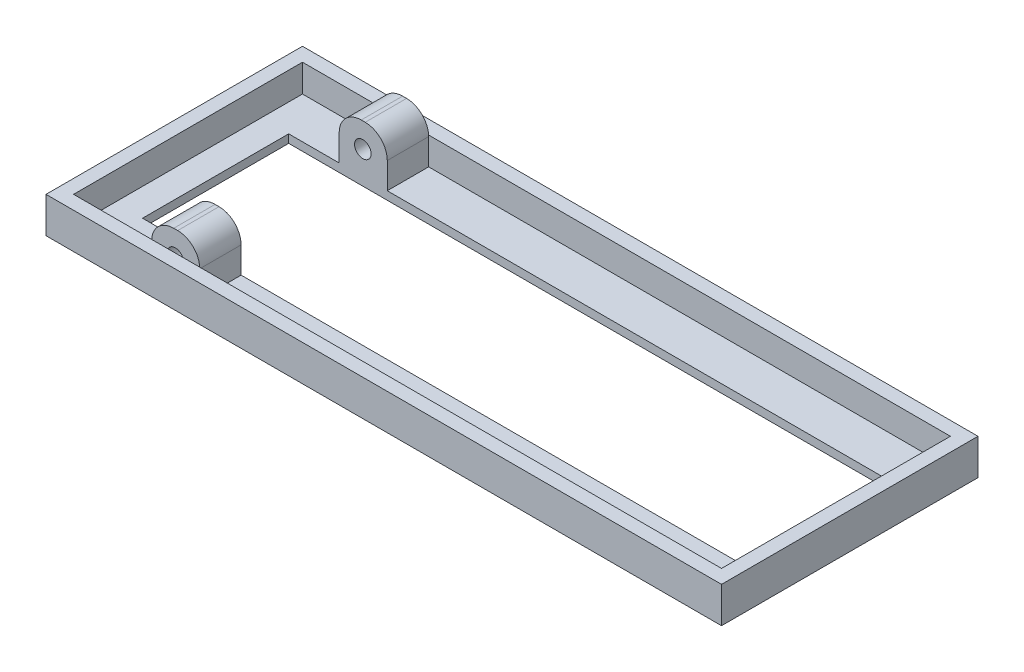
SolidWorks part; units mm, degrees
ref_plane "Front Plane" through (0, 0, 0) normal (0, 0, 1) x (1, 0, 0)
ref_plane "Top Plane" through (0, 0, 0) normal (0, 1, 0) x (1, 0, 0)
ref_plane "Right Plane" through (0, 0, 0) normal (1, 0, 0) x (0, 0, -1)
sketch "Sketch1" plane through (0, 0, 0) normal (0, 1, 0) x (1, 0, 0)
  line L0 (1125.8144, 1330.2208) -> (1275.8144, 1330.2208) construction
  line L1 (1275.8144, 1330.2208) -> (1275.8144, 1130.2208) construction
  line L2 (3575.3144, 400.2208) -> (3575.3144, 600.2208) construction
  line L3 (3575.3144, 600.2208) -> (3425.3144, 600.2208) construction
  line L5 (1275.8144, 1130.2208) -> (3425.3144, 1130.2208)
  line L6 (1275.8144, 1130.2208) -> (1275.8144, 600.2208)
  line L7 (1275.8144, 600.2208) -> (3425.3144, 600.2208)
  line L8 (3425.3144, 1130.2208) -> (3425.3144, 600.2208)
  line L13 (1125.8144, 1330.2208) -> (3575.3144, 1330.2208)
  line L14 (1125.8144, 1330.2208) -> (1125.8144, 400.2208)
  line L15 (1125.8144, 400.2208) -> (3575.3144, 400.2208)
  line L16 (3575.3144, 1330.2208) -> (3575.3144, 400.2208)
sketch "Sketch4" plane through (0, 0, 0) normal (0, 1, 0) x (1, 0, 0)
  line L0 (1125.8144, 1330.2208) -> (1275.8144, 1330.2208) construction
  line L1 (1275.8144, 1330.2208) -> (1275.8144, 1130.2208) construction
  line L2 (3575.3144, 400.2208) -> (3575.3144, 600.2208) construction
  line L3 (3575.3144, 600.2208) -> (3425.3144, 600.2208) construction
  line L4 (1275.8144, 1130.2208) -> (3425.3144, 1130.2208)
  line L5 (1275.8144, 1130.2208) -> (1275.8144, 600.2208)
  line L6 (1275.8144, 600.2208) -> (3425.3144, 600.2208)
  line L7 (3425.3144, 1130.2208) -> (3425.3144, 600.2208)
  line L8 (1125.8144, 1330.2208) -> (3575.3144, 1330.2208)
  line L9 (1125.8144, 1330.2208) -> (1125.8144, 400.2208)
  line L10 (1125.8144, 400.2208) -> (3575.3144, 400.2208)
  line L11 (3575.3144, 1330.2208) -> (3575.3144, 400.2208)
extrude "Boss-Extrude2" add sketch "Sketch4" along normal blind 30
sketch "Sketch5" plane through (0, 30, 0) normal (0, 1, 0) x (1, 0, 0)
  line L0 (1175.8144, 1280.2208) -> (1175.8144, 450.2208)
  line L1 (2350.5644, 1330.2208) -> (2350.5644, 400.2208) construction
  line L2 (3575.3144, 1330.2208) -> (1125.8144, 1330.2208) construction
  line L3 (1125.8144, 1330.2208) -> (1125.8144, 400.2208)
  line L4 (1125.8144, 400.2208) -> (3575.3144, 400.2208)
  line L5 (3575.3144, 1330.2208) -> (3575.3144, 400.2208)
  line L6 (3525.3144, 1280.2208) -> (3525.3144, 450.2208)
  line L9 (1125.8144, 400.2208) -> (3575.3144, 400.2208) construction
  line L10 (1175.8144, 1280.2208) -> (3525.3144, 1280.2208)
  line L11 (1175.8144, 450.2208) -> (3525.3144, 450.2208)
  line L12 (3575.3144, 1330.2208) -> (1125.8144, 1330.2208)
  point P7 (2350.5644, 450.2208)
  point P17 (2350.5644, 1280.2208)
sketch "Sketch6" plane through (0, 30, 0) normal (0, 1, 0) x (1, 0, 0)
  line L0 (1175.8144, 1280.2208) -> (1175.8144, 450.2208)
  line L1 (2350.5644, 1330.2208) -> (2350.5644, 400.2208) construction
  line L2 (1125.8144, 1330.2208) -> (1125.8144, 400.2208)
  line L3 (1125.8144, 400.2208) -> (3575.3144, 400.2208)
  line L4 (3575.3144, 1330.2208) -> (3575.3144, 400.2208)
  line L5 (3525.3144, 1280.2208) -> (3525.3144, 450.2208)
  line L6 (1175.8144, 1280.2208) -> (3525.3144, 1280.2208)
  line L7 (1175.8144, 450.2208) -> (3525.3144, 450.2208)
  line L8 (3575.3144, 1330.2208) -> (1125.8144, 1330.2208)
  point P6 (2350.5644, 450.2208)
  point P10 (2350.5644, 1280.2208)
extrude "Boss-Extrude3" add sketch "Sketch6" along normal blind 100
sketch "Sketch7" plane through (0, 30, 0) normal (0, 1, 0) x (1, 0, 0)
  line L0 (1275.8144, 1130.2208) -> (1546.0948, 1130.2208) construction
  line L1 (3425.3144, 1130.2208) -> (1275.8144, 1130.2208) construction
  line L2 (3525.3144, 1280.2208) -> (1175.8144, 1280.2208) construction
  line L3 (1275.8144, 865.2208) -> (3425.3144, 865.2208) construction
  line L4 (1458.8863, 1130.2208) -> (1458.8863, 1280.2208)
  line L5 (1458.8863, 1280.2208) -> (1633.3034, 1280.2208)
  line L6 (1633.3034, 1130.2208) -> (1633.3034, 1280.2208)
  line L7 (1275.8144, 1130.2208) -> (1275.8144, 600.2208) construction
  line L8 (3425.3144, 600.2208) -> (3425.3144, 1130.2208) construction
  line L9 (1458.8863, 1130.2208) -> (1633.3034, 1130.2208)
  line L10 (1458.8863, 600.2208) -> (1633.3034, 600.2208)
  line L11 (1633.3034, 600.2208) -> (1633.3034, 450.2208)
  line L12 (1458.8863, 450.2208) -> (1633.3034, 450.2208)
  line L13 (1458.8863, 600.2208) -> (1458.8863, 450.2208)
sketch "Sketch8" plane through (0, 30, 0) normal (0, 1, 0) x (1, 0, 0)
  line L0 (1275.8144, 1130.2208) -> (1546.0948, 1130.2208) construction
  line L1 (1458.8863, 1130.2208) -> (1458.8863, 1280.2208)
  line L2 (1458.8863, 1280.2208) -> (1633.3034, 1280.2208)
  line L3 (1633.3034, 1130.2208) -> (1633.3034, 1280.2208)
  line L4 (1458.8863, 1130.2208) -> (1633.3034, 1130.2208)
  line L5 (1458.8863, 600.2208) -> (1633.3034, 600.2208)
  line L6 (1633.3034, 600.2208) -> (1633.3034, 450.2208)
  line L7 (1458.8863, 450.2208) -> (1633.3034, 450.2208)
  line L8 (1458.8863, 600.2208) -> (1458.8863, 450.2208)
extrude "Boss-Extrude4" add sketch "Sketch8" along normal blind 175
sketch "Sketch9" plane through (0, 0, -1130.2208) normal (0, 0, 1) x (1, 0, 0)
  line L5 (1631.8345, 203.6281) -> (1457.4175, 29.211) construction
  circle A0 centre (1544.626, 116.4196) radius 30
sketch "Sketch10" plane through (0, 0, -1130.2208) normal (0, 0, 1) x (1, 0, 0)
  circle A0 centre (1544.626, 116.4196) radius 30
extrude "Cut-Extrude1" cut sketch "Sketch10" against normal blind 150 and the other way blind 680
fillet "Fillet1" radius 80 4 edges at (1633.3034, 205, -525.2208) (1458.8863, 205, -525.2208) (1458.8863, 205, -1205.2208) (1633.3034, 205, -1205.2208)
